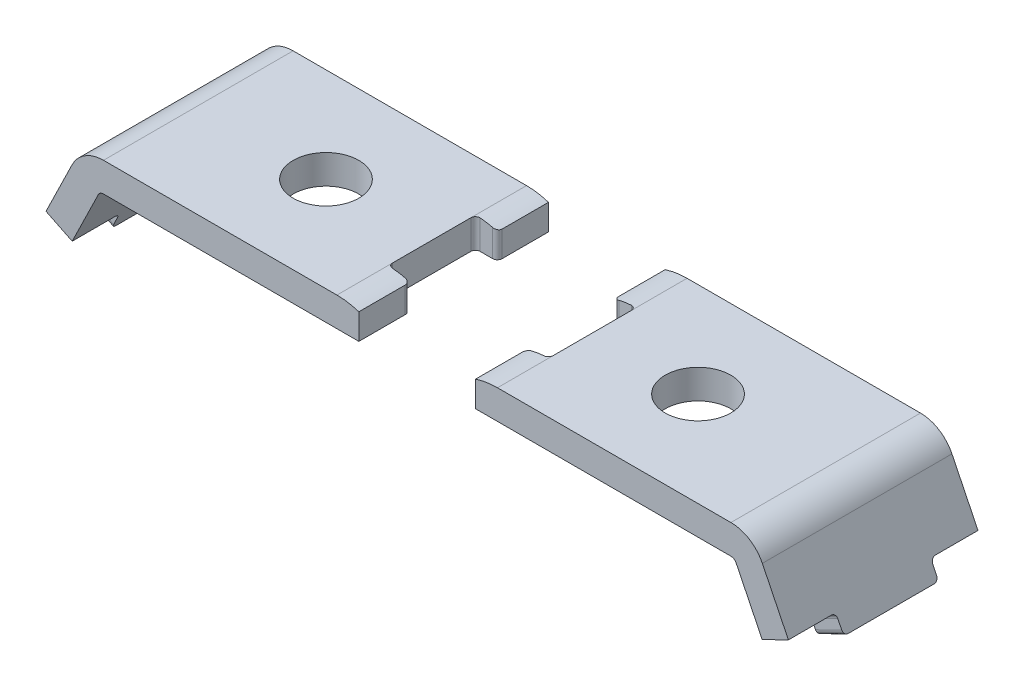
SolidWorks part; units mm, degrees
ref_plane "Front Plane" through (0, 0, 0) normal (0, 0, 1) x (1, 0, 0)
ref_plane "Top Plane" through (0, 0, 0) normal (0, 1, 0) x (1, 0, 0)
ref_plane "Right Plane" through (0, 0, 0) normal (1, 0, 0) x (0, 0, -1)
sketch "Sketch1" plane through (0, 0, 0) normal (0, 0, 1) x (1, 0, 0)
  line L0 (-12.7, 6.35) -> (-68.2932, 6.35) construction
  line L1 (-75.1393, 2.076) -> (-82.55, -13.0867) construction
  line L2 (-12.7, 0) -> (-68.2932, 0) construction
  line L3 (-69.4342, -0.7123) -> (-76.8449, -15.875) construction
  line L4 (-82.55, -13.0867) -> (-76.8449, -15.875) construction
  line L5 (-12.7, 6.35) -> (-12.7, 0) construction
  arc A0 (-68.2932, 6.35) -> (-75.1393, 2.076) centre (-68.2932, -1.27) ccw construction
  arc A1 (-68.2932, 0) -> (-69.4342, -0.7123) centre (-68.2932, -1.27) ccw construction
  point P4 (-17.4752, 6.35)
  point P6 (-73.0504, 6.35)
  point P8 (-82.55, -13.0867)
  point P9 (-12.7, 6.35)
  point P15 (-12.7, 5.588)
  dimension "D4" = 7.62
  dimension "D1" = 12.7
  dimension "Length" = 69.85
  dimension "D2" = 4.7752
  dimension "Height" = 22.225
  dimension "D3" = 60.3504
  dimension "D5" = 0.762
  dimension "Thickness" = 6.35
sketch "Sketch2" plane through (0, 0, 0) normal (1, 0, 0) x (0, 0, -1)
  line L0 (-20.6375, 0) -> (20.6375, 0) construction
  point P4 (0, 0)
  point P10 (-20.6375, 0)
  dimension "Width" = 41.275
sketch "Sketch3" plane through (0, 0, 0) normal (0, 1, 0) x (1, 0, 0)
  line L0 (-12.7, 0) -> (-68.2932, 0) construction
  line L1 (-12.7, 9.525) -> (-12.7, -9.525) construction
  line L2 (-12.7, -9.525) -> (-17.4752, -9.525) construction
  line L3 (-17.4752, -9.525) -> (-17.4752, 9.525) construction
  line L4 (-17.4752, 9.525) -> (-12.7, 9.525) construction
  circle A0 centre (-40.4939, 0) radius 7.1438 construction
  point P8 (-12.7, 0)
  dimension "Mounting Hole Dia." = 14.2875
  dimension "D2" = 4.7752
  dimension "D3" = 19.05
  dimension "Throat Depth" = 15.875
ref_plane "Plane1" through (-82.55, -13.0867, 0) normal (0.8984, -0.4391, 0) x (0, 0, -1)
sketch "Sketch4" plane through (-82.55, -13.0867, 0) normal (0.8984, -0.4391, 0) x (0, 0, -1)
  line L0 (0, 16.8768) -> (0, 0) construction
  line L1 (10.3251, 0) -> (20.6375, 0) construction
  line L2 (10.3251, 0) -> (10.3251, 3.9624) construction
  line L3 (10.3251, 3.9624) -> (20.6375, 3.9624) construction
  line L4 (20.6375, 0) -> (20.6375, 3.9624) construction
  line L5 (0, 16.8768) -> (0, 0) construction
  line L6 (-10.3251, 0) -> (-10.3251, 3.9624) construction
  line L7 (-10.3251, 0) -> (-20.6375, 0) construction
  line L8 (-20.6375, 0) -> (-20.6375, 3.9624) construction
  line L9 (-10.3251, 3.9624) -> (-20.6375, 3.9624) construction
  dimension "D1" = 3.9624
  dimension "D2" = 10.3251
sketch "Sketch5" plane through (0, 0, 0) normal (0, 0, 1) x (1, 0, 0)
  line L0 (-12.7, 6.35) -> (-68.2932, 6.35) construction
  line L1 (-12.7, 6.35) -> (-12.7, 0) construction
  line L2 (-12.7, 0) -> (-68.2932, 0) construction
  line L3 (-69.4342, -0.7123) -> (-76.8449, -15.875) construction
  line L4 (-82.55, -13.0867) -> (-76.8449, -15.875) construction
  line L5 (-75.1393, 2.076) -> (-82.55, -13.0867) construction
  line L6 (-17.4752, 6.35) -> (-68.2932, 6.35)
  line L7 (-12.7, 5.588) -> (-12.7, 0)
  line L8 (-12.7, 0) -> (-68.2932, 0)
  line L9 (-69.4342, -0.7123) -> (-76.8449, -15.875)
  line L10 (-82.55, -13.0867) -> (-76.8449, -15.875)
  line L11 (-75.1393, 2.076) -> (-82.55, -13.0867)
  arc A0 (-68.2932, 6.35) -> (-75.1393, 2.076) centre (-68.2932, -1.27) ccw construction
  arc A1 (-68.2932, 0) -> (-69.4342, -0.7123) centre (-68.2932, -1.27) ccw construction
  arc A2 (-68.2932, 6.35) -> (-75.1393, 2.076) centre (-68.2932, -1.27) ccw
  arc A3 (-68.2932, 0) -> (-69.4342, -0.7123) centre (-68.2932, -1.27) ccw
  arc A4 (-17.4752, 6.35) -> (-12.7, 5.588) centre (-17.4752, -8.9933) cw
extrude "Boss-Extrude1" add sketch "Sketch5" along normal up to vertex (20.6375 mm away) and the other way up to vertex (20.6375 mm away) up to point (0, 0, 20.6375) other way up to point (0, 0, -20.6375)
sketch "Sketch6" plane through (0, 6.35, 0) normal (0, 1, 0) x (1, 0, 0)
  line L0 (-17.4752, 9.525) -> (-12.7, 9.525) construction
  line L1 (-12.7, 9.525) -> (-12.7, -9.525) construction
  line L2 (-17.4752, -9.525) -> (-17.4752, 9.525) construction
  line L3 (-12.7, -9.525) -> (-17.4752, -9.525) construction
  line L4 (-17.4752, 9.525) -> (-12.7, 9.525)
  line L5 (-12.7, 9.525) -> (-12.7, -9.525)
  line L7 (-17.4752, -9.525) -> (-17.4752, 9.525)
  line L8 (-12.7, -9.525) -> (-17.4752, -9.525)
  circle A0 centre (-40.4939, 0) radius 7.1438 construction
  circle A1 centre (-40.4939, 0) radius 7.1438
extrude "Cut-Extrude1" cut sketch "Sketch6" against normal through all
sketch "Sketch7" plane through (-396.8726, -656.207, 0) normal (0.8984, -0.4391, 0) x (0, 0, 1)
  line L0 (20.6375, -715.823) -> (20.6375, -719.7854) construction
  line L1 (10.3251, -715.823) -> (20.6375, -715.823) construction
  line L2 (10.3251, -719.7854) -> (20.6375, -719.7854) construction
  line L3 (10.3251, -715.823) -> (10.3251, -719.7854) construction
  line L4 (-10.3251, -715.823) -> (-10.3251, -719.7854) construction
  line L5 (-10.3251, -715.823) -> (-20.6375, -715.823) construction
  line L6 (-20.6375, -715.823) -> (-20.6375, -719.7854) construction
  line L7 (-10.3251, -719.7854) -> (-20.6375, -719.7854) construction
  line L8 (20.6375, -715.823) -> (20.6375, -719.7854)
  line L9 (10.3251, -715.823) -> (20.6375, -715.823)
  line L10 (10.3251, -719.7854) -> (20.6375, -719.7854)
  line L11 (10.3251, -715.823) -> (10.3251, -719.7854)
  line L12 (-10.3251, -715.823) -> (-10.3251, -719.7854)
  line L13 (-10.3251, -715.823) -> (-20.6375, -715.823)
  line L14 (-20.6375, -715.823) -> (-20.6375, -719.7854)
  line L15 (-10.3251, -719.7854) -> (-20.6375, -719.7854)
extrude "Cut-Extrude 3" cut sketch "Sketch7" along normal through all
fillet "Fillet1" radius 1.016 8 edges at (-79.6975, -14.4808, -10.3251) (-77.9576, -10.9209, -10.3251) (-79.6975, -14.4808, 10.3251) (-77.9576, -10.9209, 10.3251) (-12.7, 2.794, 9.525) (-17.4752, 3.175, 9.525) (-12.7, 2.794, -9.525) (-17.4752, 3.175, -9.525)
mirror "Mirror4" about plane through (0, 0, 0) normal (1, 0, 0) of bodies 103 107
